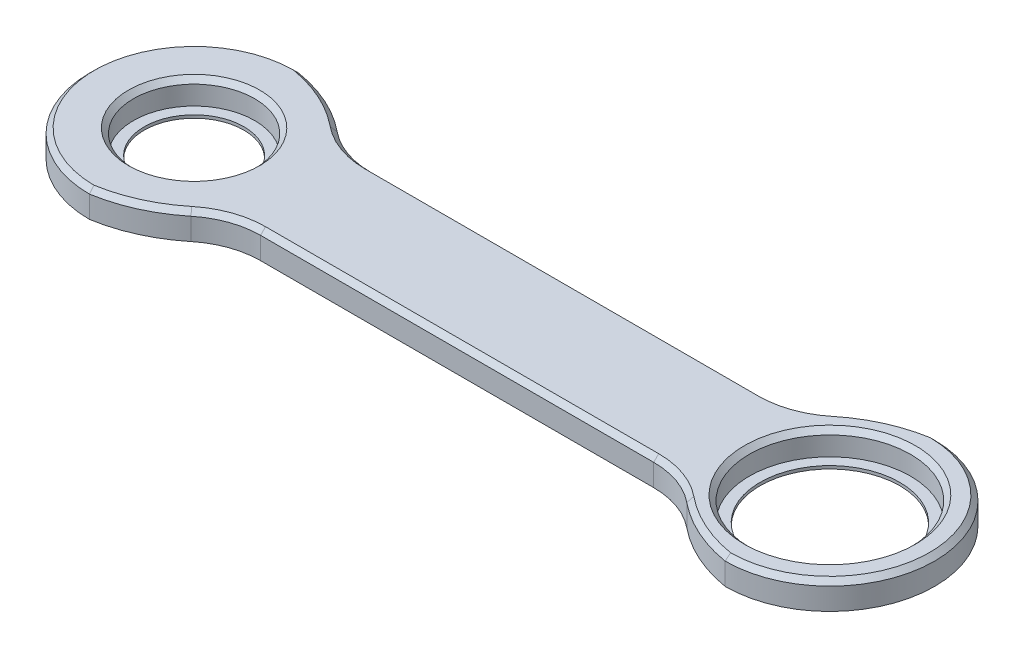
SolidWorks part; units mm, degrees
ref_plane "Front Plane" through (0, 0, 0) normal (0, 0, 1) x (1, 0, 0)
ref_plane "Top Plane" through (0, 0, 0) normal (0, 1, 0) x (1, 0, 0)
ref_plane "Right Plane" through (0, 0, 0) normal (1, 0, 0) x (0, 0, -1)
sketch "Sketch1" plane through (0, 0, 0) normal (0, 1, 0) x (1, 0, 0)
  line L0 (63.75, 0) -> (-63.75, 0) construction
  line L1 (63.75, -21) -> (-63.75, -21)
  line L2 (63.75, 21) -> (-63.75, 21)
  line L3 (-39.4205, 27.2988) -> (39.4205, 27.2988) construction
  line L4 (-39.4205, 43.5976) -> (39.4205, 43.5976)
  line L5 (-39.4205, 11) -> (39.4205, 11)
  line L6 (-39.4205, -27.2988) -> (39.4205, -27.2988) construction
  line L7 (-39.4205, -11) -> (39.4205, -11)
  line L8 (-39.4205, -43.5976) -> (39.4205, -43.5976)
  arc A0 (63.75, -21) -> (63.75, 21) centre (63.75, 0) ccw
  arc A1 (-63.75, 21) -> (-63.75, -21) centre (-63.75, 0) ccw
  circle A2 centre (-63.75, 0) radius 12.15
  arc A3 (-39.4205, 43.5976) -> (-39.4205, 11) centre (-39.4205, 27.2988) ccw
  arc A4 (39.4205, 11) -> (39.4205, 43.5976) centre (39.4205, 27.2988) ccw
  arc A5 (-39.4205, -11) -> (-39.4205, -43.5976) centre (-39.4205, -27.2988) ccw
  arc A6 (39.4205, -43.5976) -> (39.4205, -11) centre (39.4205, -27.2988) ccw
  circle A7 centre (63.75, 0) radius 16.15
  point P2 (0, 0)
  point P12 (0, 27.2988)
  point P19 (0, -27.2988)
  dimension "D2" = 24.3
  dimension "D3" = 21
  dimension "D6" = 32.3
  dimension "D1" = 127.5
  dimension "D4" = 11
  dimension "D5" = 11
extrude "Boss-Extrude1" add sketch "Sketch1" along normal blind 5.4 contours A6 L1 A0 L2 A4 L5 A3 A1 A5 L7 A7 A2 region at (-6.5789, 0, 0)
fillet "Fillet1" radius 30 4 edges at (-54.4529, 2.7, -21) (54.4529, 2.7, -21) (54.4529, 2.7, 21) (-54.4529, 2.7, 21)
chamfer "Chamfer1" distance 1 angle 45 14 edges at (63.75, 5.4, 16.15) (-63.75, 5.4, 12.15) (0, 5.4, -11) (-44.8841, 5.4, -11.943) (44.8841, 5.4, -11.943) (-56.3192, 5.4, -18.7473) (56.3192, 5.4, -18.7473) (-84.75, 5.4, 0) (84.75, 5.4, 0) (-56.3192, 5.4, 18.7473) (56.3192, 5.4, 18.7473) (-44.8841, 5.4, 11.943) (44.8841, 5.4, 11.943) (0, 5.4, 11)
sketch "Sketch2" plane through (0, 0, 0) normal (0, -1, 0) x (1, 0, 0)
  circle A0 centre (-63.75, 0) radius 10
  circle A1 centre (-63.75, 0) radius 14.7553
  circle A2 centre (63.75, 0) radius 14
  circle A3 centre (63.75, 0) radius 19.0252
  dimension "D1" = 20
  dimension "D2" = 28
extrude "Boss-Extrude2" add sketch "Sketch2" against normal blind 0.6
